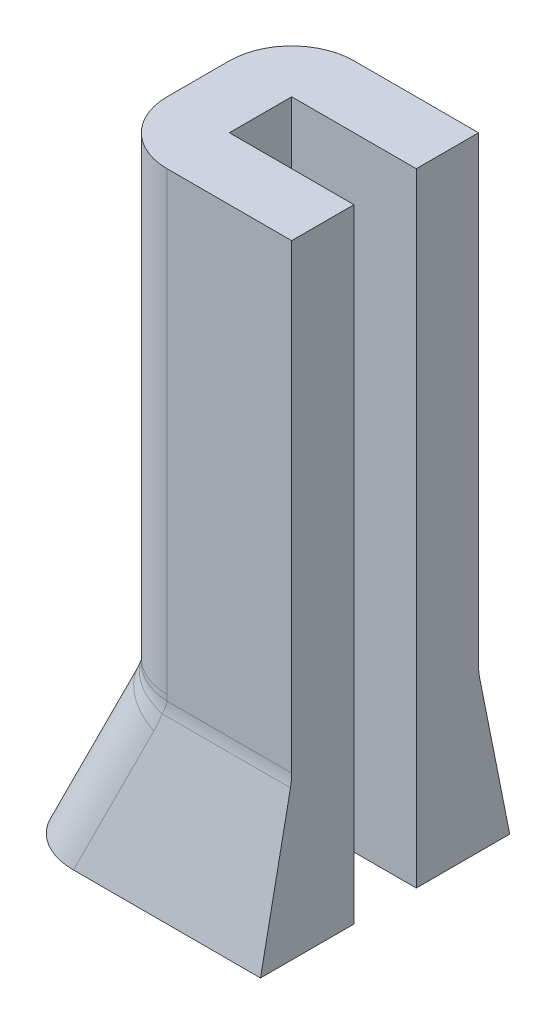
SolidWorks part; units mm, degrees
ref_plane "Front Plane" through (0, 0, 0) normal (0, 0, 1) x (1, 0, 0)
ref_plane "Top Plane" through (0, 0, 0) normal (0, 1, 0) x (1, 0, 0)
ref_plane "Right Plane" through (0, 0, 0) normal (1, 0, 0) x (0, 0, -1)
sketch "Sketch1" plane through (0, 0, 0) normal (0, 1, 0) x (1, 0, 0)
  line L0 (-5.08, 3.81) -> (2.54, 3.81)
  line L1 (-2.54, 1.27) -> (2.54, 1.27)
  line L2 (-2.54, 1.27) -> (-2.54, -1.27)
  line L3 (-2.54, -1.27) -> (2.54, -1.27)
  line L5 (-2.54, 1.27) -> (2.54, -1.27) construction
  line L6 (-2.54, -1.27) -> (2.54, 1.27) construction
  line L8 (-5.08, -3.81) -> (2.54, -3.81)
  line L9 (-5.08, 3.81) -> (-5.08, -3.81)
  line L10 (2.54, 3.81) -> (2.54, 1.27)
  line L11 (2.54, -1.27) -> (2.54, -3.81)
  line L12 (-5.08, 3.81) -> (5.08, 3.81) construction
  line L13 (5.08, 3.81) -> (5.08, -3.81) construction
  line L14 (2.54, 1.27) -> (2.54, -1.27) construction
  line L15 (-5.08, -3.81) -> (5.08, -3.81) construction
  point P0 (0, 0)
  dimension "D1" = 2.54
  dimension "D2" = 5.08
  dimension "D3" = 2.54
extrude "Boss-Extrude1" add sketch "Sketch1" along normal blind 25.4
sketch "Sketch2" plane through (0, 0, 0) normal (0, -1, 0) x (1, 0, 0)
  line L0 (2.54, -1.27) -> (2.54, -3.81) construction
  line L1 (-7.62, 5.08) -> (2.54, 5.08)
  line L2 (-7.62, 5.08) -> (-7.62, -5.08)
  line L3 (-7.62, -5.08) -> (2.54, -5.08)
  line L4 (2.54, 5.08) -> (2.54, 1.27)
  line L5 (-7.62, 5.08) -> (2.54, -5.08) construction
  line L6 (-7.62, -5.08) -> (2.54, 5.08) construction
  line L7 (-2.54, -1.27) -> (2.54, -1.27) construction
  line L8 (-2.54, 1.27) -> (-2.54, -1.27) construction
  line L9 (2.54, 1.27) -> (-2.54, 1.27) construction
  line L10 (-2.54, -1.27) -> (2.54, -1.27)
  line L11 (-2.54, 1.27) -> (-2.54, -1.27)
  line L12 (2.54, 1.27) -> (-2.54, 1.27)
  line L13 (2.54, -1.27) -> (2.54, -5.08)
  point P0 (-2.54, 0)
  point P7 (0, 0)
  dimension "D1" = 10.16
ref_plane "Plane1" through (0, 6.35, 0) normal (0, -1, 0) x (-1, 0, 0)
sketch "Sketch3" plane through (0, 6.35, 0) normal (0, -1, 0) x (-1, 0, 0)
  line L8 (-2.54, -1.27) -> (-2.54, -3.81)
  line L9 (-2.54, -3.81) -> (5.08, -3.81)
  line L10 (5.08, -3.81) -> (5.08, 3.81)
  line L11 (5.08, 3.81) -> (-2.54, 3.81)
  line L12 (-2.54, 3.81) -> (-2.54, 1.27)
  line L13 (-2.54, 1.27) -> (2.54, 1.27)
  line L14 (2.54, 1.27) -> (2.54, -1.27)
  line L15 (2.54, -1.27) -> (-2.54, -1.27)
  line L16 (-2.54, -1.27) -> (-2.54, -3.81)
  line L17 (-2.54, -3.81) -> (5.08, -3.81)
  line L18 (5.08, -3.81) -> (5.08, 3.81)
  line L19 (5.08, 3.81) -> (-2.54, 3.81)
  line L20 (-2.54, 3.81) -> (-2.54, 1.27)
  line L21 (-2.54, 1.27) -> (2.54, 1.27)
  line L22 (2.54, 1.27) -> (2.54, -1.27)
  line L23 (2.54, -1.27) -> (-2.54, -1.27)
  dimension "D1" = 0
loft "Loft1" add profiles "Sketch2", "Sketch3" connector at (-7.62, 0, -5.08) connector at (-5.08, 6.35, -3.81)
fillet "Fillet1" radius 2.54 7 edges
